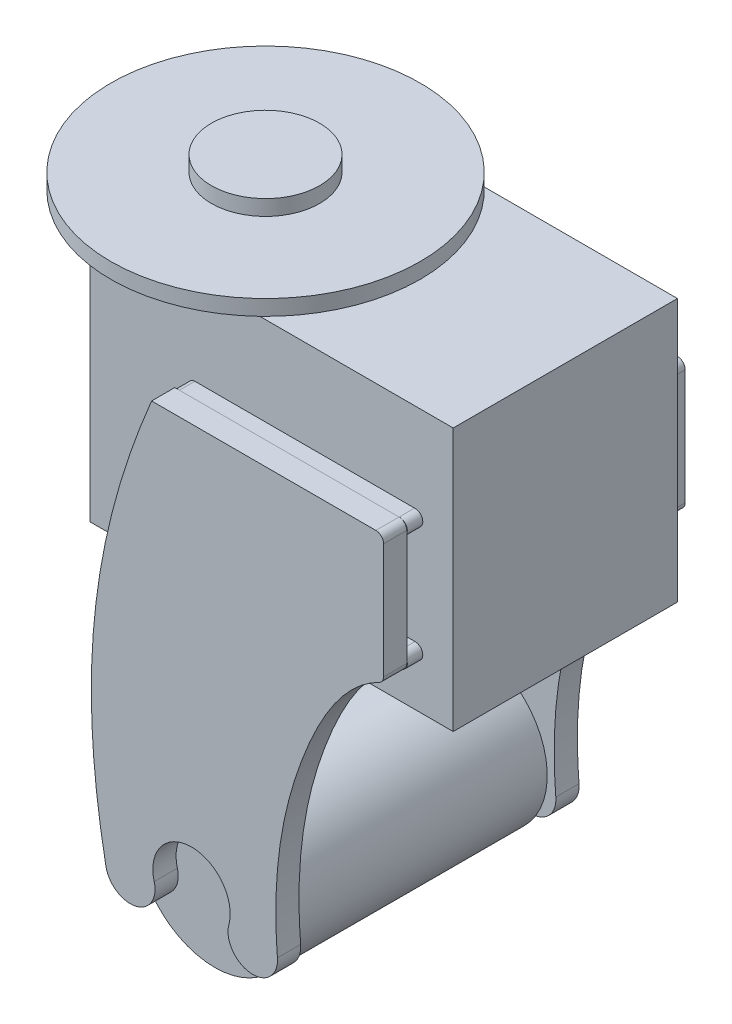
SolidWorks part; units mm, degrees
ref_plane "Front Plane" through (0, 0, 0) normal (0, 0, 1) x (1, 0, 0)
ref_plane "Top Plane" through (0, 0, 0) normal (0, 1, 0) x (1, 0, 0)
ref_plane "Right Plane" through (0, 0, 0) normal (1, 0, 0) x (0, 0, -1)
sketch "Sketch1" plane through (0, 0, 0) normal (0, 1, 0) x (1, 0, 0)
  line L1 (23.5, 14.5) -> (-23.5, 14.5)
  line L2 (23.5, 14.5) -> (23.5, -14.5)
  line L3 (23.5, -14.5) -> (-23.5, -14.5)
  line L4 (-23.5, 14.5) -> (-23.5, -14.5)
  line L5 (23.5, 14.5) -> (-23.5, -14.5) construction
  line L6 (23.5, -14.5) -> (-23.5, 14.5) construction
  point P0 (0, 0)
  dimension "D1" = 47
  dimension "D2" = 29
extrude "Boss-Extrude1" add sketch "Sketch1" against normal blind 34
sketch "Sketch2" plane through (0, 0, -14.5) normal (0, 0, -1) x (-1, 0, 0)
  line L0 (-18.5, -11.4741) -> (10.5, -11.4741)
  line L1 (-19.5, -12.4741) -> (-19.5, -27.3692)
  line L7 (-23.5, -34) -> (-23.5, 0) construction
  arc A0 (-5.7706, -65.7051) -> (0.5097, -65.1362) centre (-2.5812, -65.9647) ccw
  arc A1 (16.4014, -66.5724) -> (10.1688, -65.1362) centre (13.2597, -65.9647) cw
  arc A2 (0.5097, -65.1362) -> (10.1688, -65.1362) centre (5.3393, -63.8417) cw
  arc A3 (-18.943, -28.2658) -> (-19.5, -27.3692) centre (-18.5, -27.3692) cw
  arc A4 (-18.5, -11.4741) -> (-19.5, -12.4741) centre (-18.5, -12.4741) ccw
  spline S0 degree 3 poles (-18.943, -28.2658) (-14.3512, -30.5346) (-6.8166, -43.8148) (-5.0641, -57.0222) (-5.7706, -65.7051) knots 0.029971 0.029971 0.029971 0.029971 0.417816 1 1 1 1
  spline S1 degree 3 poles (10.5, -11.4741) (18.3438, -30.086) (20.1849, -47.0142) (16.4014, -66.5724) knots 0 0 0 0 1 1 1 1
  point P24 (-19.5, -11.4741)
  dimension "D3" = 3.2
  dimension "D4" = 3.2
  dimension "D5" = 5
  dimension "D7" = 56.3074
  dimension "D8" = 41.5081
  dimension "D10" = 1
  dimension "D2" = 1
  dimension "D1" = 30
  dimension "D6" = 4
  dimension "D9" = 27.2885
  dimension "D11" = 15.8408
  dimension "D12" = 27.2885
extrude "Boss-Extrude2" add sketch "Sketch2" along normal blind 3 from offset 2
sketch "Sketch3" plane through (0, 0, -14.5) normal (0, 0, -1) x (-1, 0, 0)
  line L0 (10.5, -11.4741) -> (-18.5, -11.4741) construction
  line L1 (9.9, -11.4741) -> (-18.5, -11.4741)
  line L4 (23.5, 0) -> (-23.5, 0)
  line L5 (-23.5, 0) -> (-23.5, -34)
  line L6 (-23.5, -34) -> (23.5, -34)
  line L7 (23.5, -34) -> (23.5, 0)
  line L8 (23.5, 0) -> (-23.5, 0)
  line L9 (-23.5, 0) -> (-23.5, -34)
  line L10 (-23.5, -34) -> (23.5, -34)
  line L11 (23.5, -34) -> (23.5, 0)
  line L12 (-18.5666, -28.3868) -> (9.8334, -28.3868)
  line L13 (-18.5666, -13.4719) -> (9.8334, -13.4719)
  line L14 (-18.5666, -26.3868) -> (9.8334, -26.3868)
  arc A2 (-18.5666, -28.3868) -> (-18.5666, -26.3868) centre (-18.5666, -27.3868) cw
  arc A3 (-18.5, -11.4741) -> (-18.5666, -13.4719) centre (-18.5666, -12.4719) ccw
  arc A4 (9.8334, -13.4719) -> (9.9, -11.4741) centre (9.8334, -12.4719) ccw
  arc A5 (9.8334, -26.3868) -> (9.8334, -28.3868) centre (9.8334, -27.3868) cw
  spline S1 degree 3 poles (16.4014, -66.5724) (20.1849, -47.0142) (18.3438, -30.086) (10.5, -11.4741) knots 0 0 0 0 1 1 1 1 construction
  dimension "D2" = 1
  dimension "D3" = 1
  dimension "D4" = 14.9149
  dimension "D1" = 0
extrude "Boss-Extrude3" add sketch "Sketch3" along normal blind 2 contours A4 L1 A3 L13 | A5 L12 A2 L14
sketch "Sketch4" plane through (0, -11.4741, 0) normal (0, 1, 0) x (1, 0, 0)
  line L0 (-2.4185, 15.5816) -> (11.6185, 15.5816)
  line L1 (-4.4, 14.5) -> (13.6, 14.5)
  line L2 (23.5, 14.5) -> (-23.5, 14.5) construction
  line L3 (-9.9, 14.5) -> (18.5, 14.5) construction
  line L4 (-9.9, 16.5) -> (18.5, 16.5) construction
  line L5 (-9.9, 16.5) -> (18.5, 16.5)
  line L6 (-4.4, 14.5) -> (-3.2236, 15.3269)
  line L7 (12.4236, 15.3269) -> (13.6, 14.5)
  arc A0 (12.4236, 15.3269) -> (11.6185, 15.5816) centre (11.6185, 14.1816) ccw
  arc A1 (-2.4185, 15.5816) -> (-3.2236, 15.3269) centre (-2.4185, 14.1816) ccw
  point P10 (4.6, 15.5816)
  point P11 (4.6, 14.5)
  dimension "D3" = 1.4
  dimension "D1" = 18
  dimension "D2" = 5.5
  dimension "D4" = 14.0371
  dimension "D5" = 15.6473
extrude "Cut-Extrude1" cut sketch "Sketch4" against normal through all contours L1 L7 A0 L0 A1 L6
mirror "Mirror4" about plane through (0, 0, 0) normal (0, 0, 1) of "Boss-Extrude3"
mirror "Mirror5" about plane through (0, 0, 0) normal (0, 0, 1) of bodies 102
sketch "Sketch5" plane through (0, 0, -19.5) normal (0, 0, -1) x (-1, 0, 0)
  circle A0 centre (5.3393, -63.8417) radius 10
  dimension "D1" = 20
extrude "Boss-Extrude4" add sketch "Sketch5" against normal up to surface (36 mm away) from surface separate body up to face at (5.4456, -40.3305, 16.5) starting at face at (5.4456, -40.3305, -16.5)
sketch "Sketch6" plane through (0, 0, 0) normal (0, 1, 0) x (1, 0, 0)
  line L0 (-23.5, 14.5) -> (-23.5, -14.5) construction
  circle A0 centre (-15.27, 0) radius 20
  dimension "D1" = 40
  dimension "D2" = 8.23
extrude "Boss-Extrude5" add sketch "Sketch6" along normal blind 2
sketch "Sketch7" plane through (0, 2, 0) normal (0, 1, 0) x (1, 0, 0)
  circle A0 centre (-15.27, 0) radius 7
  circle A1 centre (-15.27, 0) radius 20 construction
  dimension "D1" = 14
  dimension "D2" = 0
extrude "Boss-Extrude6" add sketch "Sketch7" along normal blind 2
ref_axis "Axis1" through (-5.3393, -63.8417, -53.8514) along (0, 0, 1)
ref_plane "Plane1" through (0, 0, 0) normal (0, 0, -1) x (-1, 0, 0)
ref_point "Point1"
